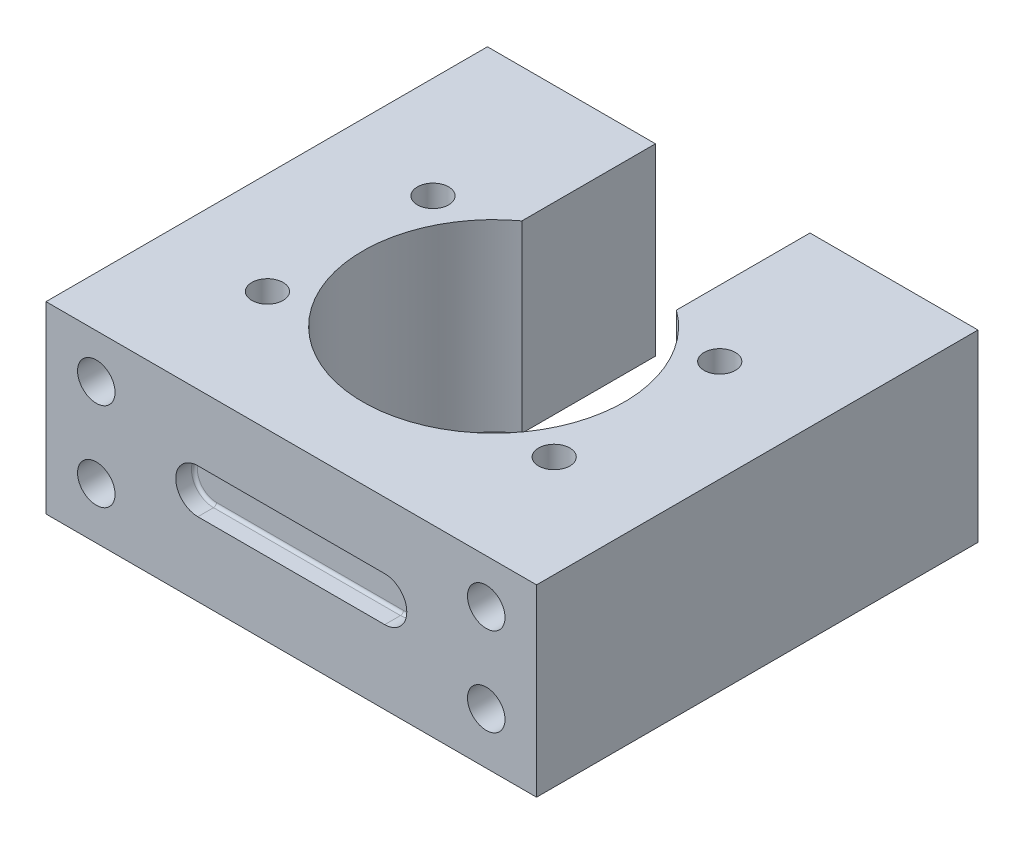
SolidWorks part; units mm, degrees
material "Low Carbon Steel"
ref_plane "Front Plane" through (0, 0, 0) normal (0, 0, 1) x (1, 0, 0)
ref_plane "Top Plane" through (0, 0, 0) normal (0, 1, 0) x (1, 0, 0)
ref_plane "Right Plane" through (0, 0, 0) normal (1, 0, 0) x (0, 0, -1)
sketch "Sketch1" plane through (0, 0, 0) normal (0, 1, 0) x (1, 0, 0)
  line L0 (-66.675, 0) -> (66.675, 0)
  line L1 (-66.675, 120) -> (66.675, 120)
  line L2 (-66.675, 120) -> (-66.675, -0.65)
  line L3 (-66.675, -0.65) -> (66.675, -0.65)
  line L4 (66.675, 120) -> (66.675, -0.65)
  dimension "D1" = 133.35
  dimension "D2" = 120.65
  dimension "D3" = 120
  dimension "D4" = 0.65
extrude "Boss-Extrude1" add sketch "Sketch1" along normal mid plane 57.15 contours L4 L0 L2 L3 | L4 L1 L2 L0 region at (0, 0, -60) region at (0, 0, 0.325)
extrude "Cut-Extrude2" cut sketch "Sketch1<3>" along normal through all and the other way through all contours L4 L0 L2 L3 region at (0, 0, 0.325)
sketch "Sketch1<3>" plane through (0, 0, 0) normal (0, 1, 0) x (1, 0, 0) same geometry as "Sketch1"
sketch "Sketch2" plane through (66.675, 0, 0) normal (1, 0, 0) x (0, 0, -1)
  line L0 (120, 28.575) -> (120, -28.575) construction
  line L1 (0, 28.575) -> (120, 28.575)
  line L2 (0, 28.575) -> (0, 21.425)
  line L3 (0, 21.425) -> (120, 21.425)
  line L4 (120, 28.575) -> (120, 21.425)
  line L5 (120, -28.575) -> (0, -28.575) construction
  dimension "D1" = 50
extrude "Cut-Extrude3" cut sketch "Sketch2" against normal through all
sketch "Sketch3" plane through (0, 21.425, 0) normal (0, 1, 0) x (1, 0, 0)
  line L0 (0, 55) -> (0, 0) construction
  circle A0 centre (0, 55) radius 35.56
  dimension "D1" = 71.12
  dimension "D2" = 55
extrude "Cut-Extrude4" cut sketch "Sketch3" against normal through all
sketch "Sketch4" plane through (0, 21.425, 0) normal (0, 1, 0) x (1, 0, 0)
  line L0 (-66.675, 120) -> (66.675, 120) construction
  line L1 (-21, 120) -> (21, 120)
  line L2 (-21, 120) -> (-21, 83.6969)
  line L3 (-21, 83.6969) -> (21, 83.6969)
  line L4 (21, 120) -> (21, 83.6969)
  line L5 (0, 0) -> (0, 83.6969) construction
  circle A0 centre (0, 55) radius 35.56 construction
  dimension "D1" = 42
extrude "Cut-Extrude5" cut sketch "Sketch4" against normal through all
hole_wizard "M10 Tapped Hole1" positions "Sketch6" profile "Sketch5" tap size "M10" standard "Peddi DIN"
sketch "Sketch6" plane through (0, 21.425, 0) normal (0, 1, 0) x (1, 0, 0)
  line L0 (38.9711, 77.5) -> (-38.9711, 32.5) construction
  line L1 (-38.9711, 32.5) -> (38.9711, 32.5) construction
  line L2 (38.9711, 32.5) -> (38.9711, 77.5) construction
  line L3 (38.9711, 77.5) -> (-38.9711, 77.5) construction
  line L4 (-38.9711, 77.5) -> (-38.9711, 32.5) construction
  arc A1 (-21, 83.6969) -> (21, 83.6969) centre (0, 55) ccw construction
  arc A2 (-21, 83.6969) -> (21, 83.6969) centre (0, 55) ccw construction
  point P0 (-38.9711, 77.5)
  point P2 (-38.9711, 32.5)
  point P4 (38.9711, 77.5)
  point P6 (38.9711, 32.5)
  dimension "D1" = 90
  dimension "D2" = 30
sketch "Sketch5" plane through (-38.9711, 21.425, -77.5) normal (1, 0, 0) x (0, 0, 1)
  line L0 (0, 0) -> (0, 30.0537)
  line L1 (0, 30.0537) -> (4.25, 27.5)
  line L2 (4.25, 27.5) -> (4.25, 0)
  line L5 (4.25, 0) -> (0, 0)
  line L10 (0, 30.0537) -> (-4.25, 27.5) construction
  line L11 (0, -6.35) -> (0, 107.95) construction
  dimension "Tap Drill Dia." = 8.5
  dimension "Tap Drill Depth" = 27.5
  dimension "Drill Angle" = 118
cosmetic thread "Hole Thread1" parameters "D1"=24.99, "D2"=10
cosmetic thread "Hole Thread2" parameters "D1"=24.99, "D2"=10
cosmetic thread "Hole Thread3" parameters "D1"=24.99, "D2"=10
cosmetic thread "Hole Thread4" parameters "D1"=24.99, "D2"=10
hole_wizard "M12 Tapped Hole1" positions "Sketch8" profile "Sketch7" tap size "M12" standard "Peddi DIN"
sketch "Sketch8" plane through (0, 0, 0) normal (0, 0, 1) x (1, 0, 0)
  line L0 (53, 9.425) -> (53, -14.575) construction
  line L2 (53, -14.575) -> (-53, -14.575) construction
  line L3 (-53, -14.575) -> (-53, 9.425) construction
  line L4 (-53, 9.425) -> (53, 9.425) construction
  line L6 (-66.675, 21.425) -> (66.675, 21.425) construction
  line L7 (0, 0) -> (0, 9.425) construction
  line L8 (66.675, 21.425) -> (66.675, -28.575) construction
  line L9 (-66.675, 21.425) -> (-66.675, -28.575) construction
  point P0 (-53, 9.425)
  point P2 (-53, -14.575)
  point P4 (53, 9.425)
  point P6 (53, -14.575)
  dimension "D1" = 12
  dimension "D2" = 24
  dimension "D3" = 106
  dimension "D4" = 13.675
  dimension "D5" = 13.675
sketch "Sketch7" plane through (-53, 9.425, 0) normal (1, 0, 0) x (0, -1, 0)
  line L0 (0, 0) -> (0, 47.0544)
  line L1 (0, 47.0544) -> (5.1, 43.99)
  line L2 (5.1, 43.99) -> (5.1, 0)
  line L5 (5.1, 0) -> (0, 0)
  line L10 (0, 47.0544) -> (-5.1, 43.99) construction
  line L11 (0, -6.35) -> (0, 107.95) construction
  dimension "Tap Drill Dia." = 10.2
  dimension "Tap Drill Depth" = 43.99
  dimension "Drill Angle" = 118
cosmetic thread "Hole Thread5" parameters "D1"=30, "D2"=12
cosmetic thread "Hole Thread6" parameters "D1"=30, "D2"=12
cosmetic thread "Hole Thread7" parameters "D1"=30, "D2"=12
cosmetic thread "Hole Thread8" parameters "D1"=30, "D2"=12
sketch "Sketch9" plane through (0, 0, 0) normal (0, 0, 1) x (1, 0, 0)
  line L0 (-53, 9.425) -> (-53, -14.575) construction
  line L1 (-25.4, -2.575) -> (25.4, -2.575) construction
  line L2 (-25.4, 3.425) -> (25.4, 3.425)
  line L4 (-25.4, -8.575) -> (25.4, -8.575)
  line L5 (-53, -2.575) -> (-25.4, -2.575) construction
  line L6 (0, 21.425) -> (0, -2.575) construction
  line L7 (-66.675, 21.425) -> (66.675, 21.425) construction
  arc A0 (-25.4, 3.425) -> (-25.4, -8.575) centre (-25.4, -2.575) ccw
  arc A1 (25.4, -8.575) -> (25.4, 3.425) centre (25.4, -2.575) ccw
  point P4 (0, -2.575)
  dimension "D1" = 12
  dimension "D2" = 50.8
extrude "Cut-Extrude6" cut sketch "Sketch9" against normal blind 5.08
fillet "Fillet1" radius 0.8128 4 edges at (0, -8.575, -5.08) (-31.4, -2.575, -5.08) (0, 3.425, -5.08) (31.4, -2.575, -5.08)
other "Freeze***"
